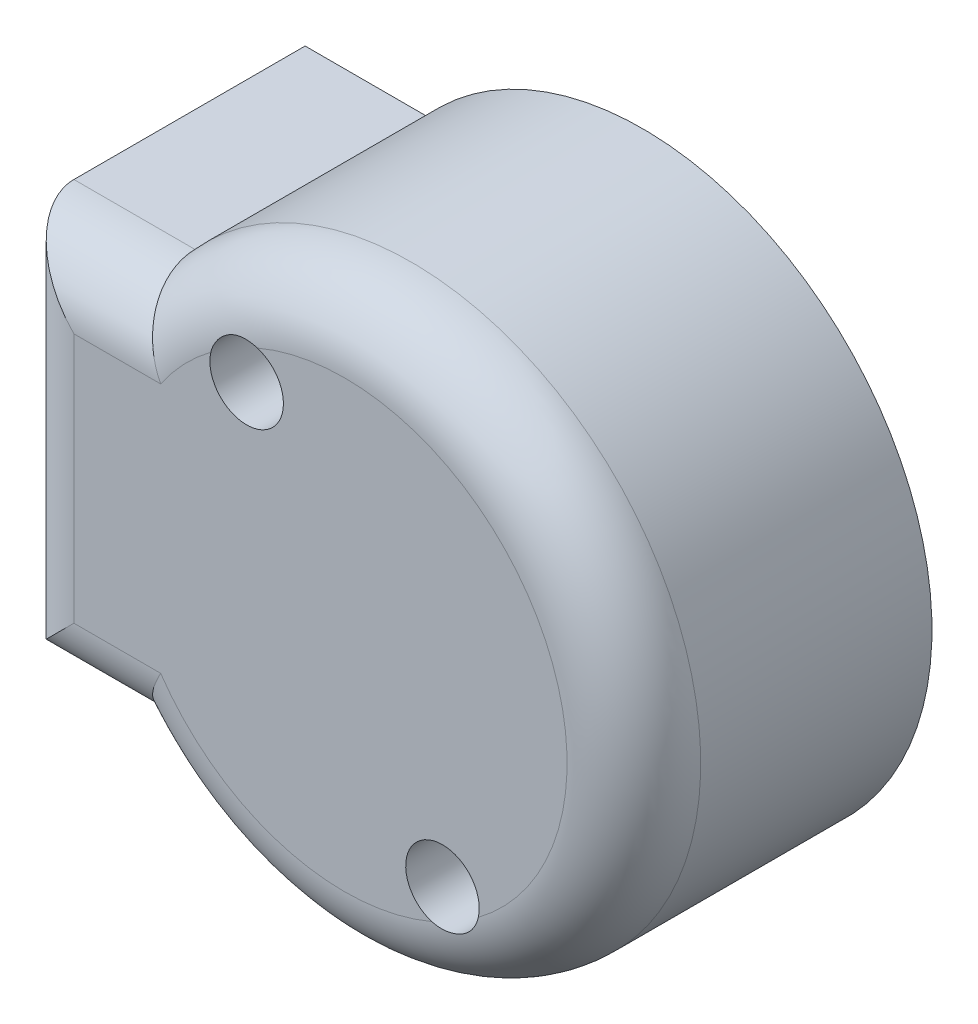
SolidWorks part; units mm, degrees
ref_plane "Front Plane" through (0, 0, 0) normal (0, 0, 1) x (1, 0, 0)
ref_plane "Top Plane" through (0, 0, 0) normal (0, 1, 0) x (1, 0, 0)
ref_plane "Right Plane" through (0, 0, 0) normal (1, 0, 0) x (0, 0, -1)
sketch "Sketch1" plane through (0, 0, 0) normal (0, 0, 1) x (1, 0, 0)
  circle A0 centre (0, 0) radius 10.9982
  circle A1 centre (0, 0) radius 7.4422 construction
  point P9 (-2.7322, -9.1753)
  dimension "D1" = 21.9964
  dimension "D2" = 14.8844
extrude "Boss-Extrude1" add sketch "Sketch1" along normal blind 11.3284
sketch "Sketch2" plane through (0, 0, 11.3284) normal (0, 0, 1) x (1, 0, 0)
  line L0 (-12.827, 0) -> (0, 0) construction
  line L2 (-12.827, 7.3025) -> (-1.9646, 7.3025)
  line L3 (-12.827, 7.3025) -> (-12.827, -7.3025)
  line L4 (-12.827, -7.3025) -> (-1.9646, -7.3025)
  line L5 (-1.9646, 7.3025) -> (-1.9646, -7.3025)
  circle A0 centre (0, 0) radius 10.9982 construction
  dimension "D1" = 12.827
  dimension "D2" = 14.605
extrude "Boss-Extrude2" add sketch "Sketch2" against normal up to surface (11.3284 mm away) up to face at (10.9982, 0, 0)
sketch "Sketch3" plane through (0, 0, 11.3284) normal (0, 0, 1) x (1, 0, 0)
  line L0 (0, 0) -> (-12.827, 0) construction
  line L1 (-12.827, 7.3025) -> (-12.827, -7.3025) construction
  line L2 (0, 0) -> (-3.7211, 6.4451) construction
  line L3 (0, 0) -> (3.7211, -6.4451) construction
  circle A0 centre (-3.7211, 6.4451) radius 1.397
  circle A1 centre (3.7211, -6.4451) radius 1.397
  circle A2 centre (0, 0) radius 7.4422 construction
  dimension "D2" = 2.794
  dimension "D1" = 60
extrude "Cut-Extrude1" cut sketch "Sketch3" against normal up to surface (11.3284 mm away) up to face at (-5.7199, 0, 0)
fillet "Fillet1" radius 2.54 4 edges at (-10.5255, -7.3025, 11.3284) (-12.827, 0, 11.3284) (-10.5255, 7.3025, 11.3284) (10.9982, 0, 11.3284)
